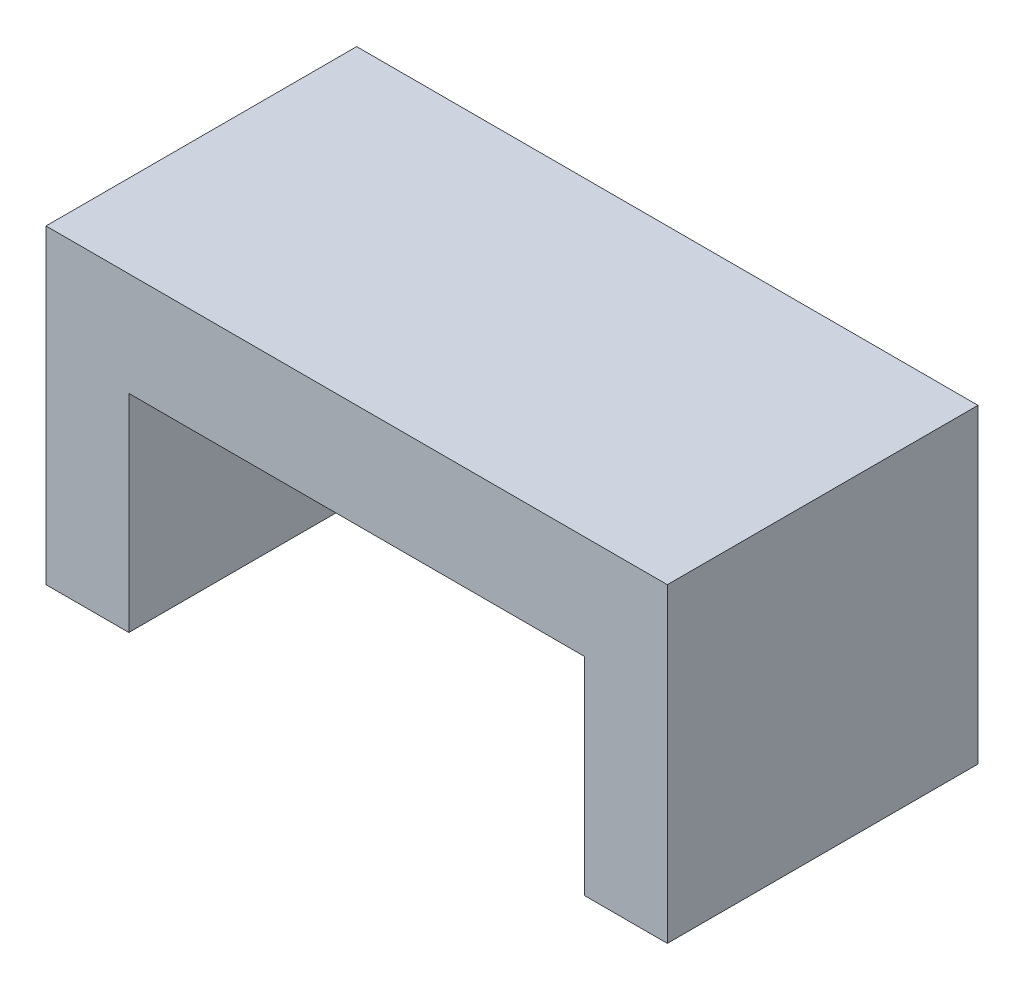
SolidWorks part; units mm, degrees
ref_plane "Front Plane" through (0, 0, 0) normal (0, 0, 1) x (1, 0, 0)
ref_plane "Top Plane" through (0, 0, 0) normal (0, 1, 0) x (1, 0, 0)
ref_plane "Right Plane" through (0, 0, 0) normal (1, 0, 0) x (0, 0, -1)
sketch "Sketch2" plane through (0, 0, 0) normal (0, 1, 0) x (1, 0, 0)
  line L0 (0, 0) -> (-13, 0) construction
  line L1 (0, -40) -> (0, 40) construction
  line L2 (-11, -7.5) -> (-15, -7.5)
  line L3 (-11, -7.5) -> (-11, 7.5)
  line L4 (-11, 7.5) -> (-15, 7.5)
  line L5 (-15, -7.5) -> (-15, 7.5)
  line L6 (-11, -7.5) -> (-15, 7.5) construction
  line L7 (-11, 7.5) -> (-15, -7.5) construction
  line L8 (11, 7.5) -> (15, -7.5) construction
  line L9 (11, -7.5) -> (15, 7.5) construction
  line L10 (15, -7.5) -> (15, 7.5)
  line L11 (11, 7.5) -> (15, 7.5)
  line L12 (11, -7.5) -> (11, 7.5)
  line L13 (11, -7.5) -> (15, -7.5)
  point P10 (0, 0)
  dimension "D1" = 80
  dimension "D2" = 4
  dimension "D3" = 15
  dimension "D4" = 15
extrude "Boss-Extrude1" add sketch "Sketch2" against normal blind 10
sketch "Sketch3" plane through (0, 0, 0) normal (0, 0, 1) x (1, 0, 0)
  line L0 (-15, 0) -> (15, 0)
  line L1 (-15, 0) -> (-15, 5)
  line L2 (15, 0) -> (15, 5)
  line L3 (-15, 5) -> (15, 5)
  dimension "D1" = 5
extrude "Boss-Extrude2" add sketch "Sketch3" along normal blind 7.5 and the other way blind 7.5
